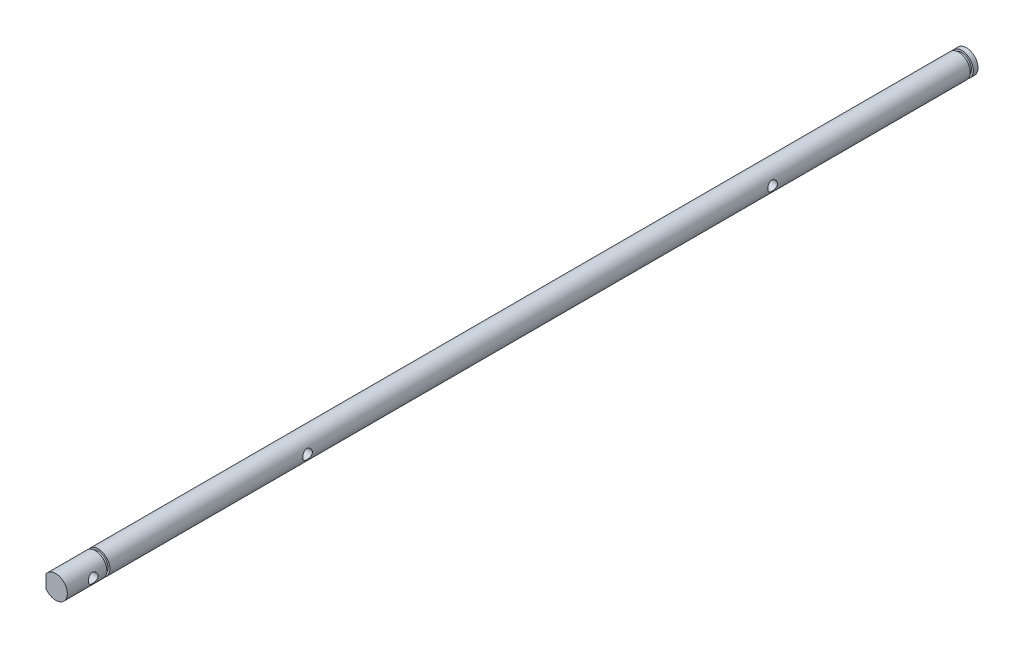
SolidWorks part; units mm, degrees
ref_plane "Front Plane" through (0, 0, 0) normal (0, 0, 1) x (1, 0, 0)
ref_plane "Top Plane" through (0, 0, 0) normal (0, 1, 0) x (1, 0, 0)
ref_plane "Right Plane" through (0, 0, 0) normal (1, 0, 0) x (0, 0, -1)
sketch "Sketch1" plane through (0, 0, 0) normal (0, 0, 1) x (1, 0, 0)
  circle A0 centre (0, 0) radius 3
  dimension "D1" = 6
extrude "Boss-Extrude1" add sketch "Sketch1" along normal blind 235
ref_axis "Axis1" [suppressed] through (0, 0, 240) along (0, 0, -1)
sketch "Sketch2" plane through (0, 0, 0) normal (0, 1, 0) x (1, 0, 0)
  line L0 (-3, 0) -> (-3, -235) construction
  line L1 (-3, -1.2) -> (-2.5, -1.2)
  line L2 (-3, -1.2) -> (-3, -2)
  line L3 (-3, -2) -> (-2.5, -2)
  line L4 (-2.5, -1.2) -> (-2.5, -2)
  line L5 (3, 0) -> (-3, 0) construction
  line L6 (-3, 0) -> (-3, -235) construction
  line L7 (-3, -224) -> (-2.5, -224)
  line L8 (-3, -224) -> (-3, -224.8)
  line L9 (-3, -224.8) -> (-2.5, -224.8)
  line L10 (-2.5, -224) -> (-2.5, -224.8)
  dimension "D1" = 0.8
  dimension "D2" = 0.5
  dimension "D3" = 2
  dimension "D4" = 224
revolve "Cut-Revolve1" cut sketch "Sketch2" angle 360 about axis through (0, 0, 240) along (0, 0, -1)
sketch "Sketch3" plane through (0, 0, 0) normal (0, 1, 0) x (1, 0, 0)
  line L0 (-3, -2) -> (-3, -224) construction
  line L1 (-3, -48) -> (-2.5, -48)
  line L2 (-3, -48) -> (-3, -58)
  line L3 (-3, -58) -> (-2.5, -58)
  line L4 (-2.5, -48) -> (-2.5, -58)
  line L5 (3, 0) -> (-3, 0) construction
  line L6 (-3, -168) -> (-2.5, -168)
  line L7 (-3, -168) -> (-3, -178)
  line L8 (-3, -178) -> (-2.5, -178)
  line L9 (-2.5, -168) -> (-2.5, -178)
  line L11 (-3, -235) -> (-2.5, -235)
  line L12 (-3, -235) -> (-3, -226)
  line L13 (-3, -226) -> (-2.5, -226)
  line L14 (-2.5, -235) -> (-2.5, -226)
  dimension "D1" = 0.5
  dimension "D2" = 48
  dimension "D3" = 10
  dimension "D4" = 120
  dimension "D5" = 9
extrude "Cut-Extrude1" cut sketch "Sketch3" against normal blind 10 and the other way blind 10
sketch "Sketch4" plane through (-2.5, 0, 0) normal (-1, 0, 0) x (0, 0, 1)
  line L0 (178, 0) -> (168, 0) construction
  line L1 (178, 1.6583) -> (178, -1.6583) construction
  line L2 (168, 1.6583) -> (168, -1.6583) construction
  line L3 (58, 0) -> (48, 0) construction
  line L4 (58, 1.6583) -> (58, -1.6583) construction
  line L5 (48, 1.6583) -> (48, -1.6583) construction
  circle A0 centre (53, 0) radius 1.25
  circle A1 centre (173, 0) radius 1.25
  dimension "D1" = 2.5
  dimension "D2" = 2.5
hole_wizard "M3 Tapped Hole1" positions "3DSketch1" profile "Sketch5" tap size "M3" standard "ISO" end condition through all
sketch3d "3DSketch1"
  point P0 (-2.5, 0, 173)
  point P3 (-2.5, 0, 53)
sketch "Sketch5" plane through (-2.5, 0, 173) normal (0, 1, 0) x (0, 0, 1)
  line L0 (0, 0) -> (0, 5.5)
  line L1 (0, 5.5) -> (1.25, 5.5)
  line L2 (1.25, 5.5) -> (1.25, 0)
  line L5 (1.25, 0) -> (0, 0)
  line L11 (0, -6.35) -> (0, 107.95) construction
  dimension "Thru Tap Drill Dia." = 2.5
  dimension "Thru Tap Drill Depth" = 5.5
cosmetic thread "Hole Thread1" parameters "D2"=3
cosmetic thread "Hole Thread2" parameters "D2"=3
ref_plane "Plane1" through (-3.5, 0, 0) normal (-1, 0, 0) x (0, 0, 1)
sketch "Sketch6" plane through (-3.5, 0, 0) normal (-1, 0, 0) x (0, 0, 1)
  line L0 (224.8, 0) -> (228.3, 0) construction
  line L1 (224.8, 2.5) -> (224.8, -2.5) construction
  circle A0 centre (228.3, 0) radius 1.25
  dimension "D1" = 2.5
  dimension "D2" = 3.5
sketch "Sketch7" plane through (-2.5, 0, 0) normal (-1, 0, 0) x (0, 0, 1)
  line L0 (224.8, 0) -> (228.3, 0) construction
  line L1 (224.8, 3) -> (224.8, -3) construction
  circle A0 centre (228.3, 0) radius 1.5
  dimension "D1" = 3
  dimension "D2" = 3.5
hole_wizard "M3x0.5 Tapped Hole1" positions "3DSketch2" profile "Sketch8" tap size "M3x0.5" standard "JIS" end condition through all
sketch3d "3DSketch2"
  point P0 (-2.5, 0, 228.3)
sketch "Sketch8" plane through (-2.5, 0, 228.3) normal (0, 1, 0) x (0, 0, 1)
  line L0 (0, 0) -> (0, 5.5)
  line L1 (0, 5.5) -> (1.25, 5.5)
  line L2 (1.25, 5.5) -> (1.25, 0)
  line L5 (1.25, 0) -> (0, 0)
  line L11 (0, -6.35) -> (0, 107.95) construction
  dimension "Thru Tap Drill Dia." = 2.5
  dimension "Thru Tap Drill Depth" = 5.5
cosmetic thread "Hole Thread3" parameters "D2"=3
